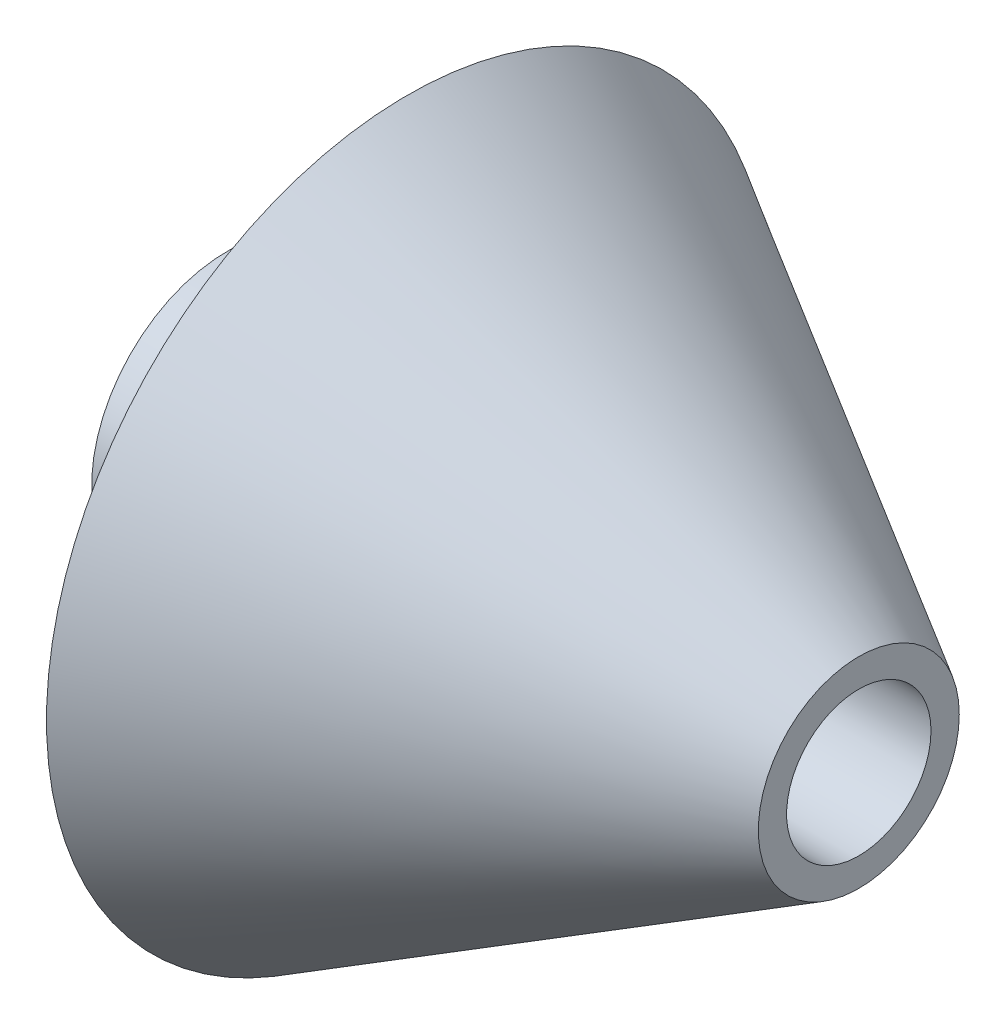
SolidWorks part; units mm, degrees
ref_plane "Alzado" through (0, 0, 0) normal (0, 0, 1) x (1, 0, 0)
ref_plane "Planta" through (0, 0, 0) normal (0, 1, 0) x (1, 0, 0)
ref_plane "Vista lateral" through (0, 0, 0) normal (1, 0, 0) x (0, 0, -1)
sketch "Croquis1" plane through (0, 0, 0) normal (1, 0, 0) x (0, 0, -1)
  line L0 (0, 7.5) -> (0, -7.5) construction
  line L1 (-7.5, 0) -> (7.5, 0) construction
  circle A0 centre (0, 0) radius 7.5
  dimension "D1" = 15
extrude "Saliente-Extruir1" add sketch "Croquis1" along normal blind 10
sketch "Croquis2" plane through (10, 0, 0) normal (1, 0, 0) x (0, 0, -1)
  circle A0 centre (0, 0) radius 20
  dimension "D1" = 40
extrude "Saliente-Extruir2" add sketch "Croquis2" along normal blind 25 draft 30
sketch "Croquis3" plane through (35, 0, 0) normal (1, 0, 0) x (0, 0, -1)
  circle A0 centre (0, 0) radius 4
  dimension "D1" = 8
extrude "Cortar-Extruir2" cut sketch "Croquis3" against normal blind 70
hole_wizard "Taladro de margen para #81" positions "Croquis3D1" profile "Croquis4" hole size "#8" standard "Ansi Inch" end condition up to next
sketch3d "Croquis3D1"
  point P0 (5, 7.4812, -0.5307)
  dimension "D1" = 5
sketch "Croquis4" plane through (5, 7.4812, -0.5307) normal (1, 0, 0) x (0, 0.0708, 0.9975)
  line L0 (0, 0) -> (0, 3.5)
  line L1 (0, 3.5) -> (2.2479, 3.5)
  line L2 (2.2479, 3.5) -> (2.2479, 0)
  line L5 (2.2479, 0) -> (0, 0)
  line L11 (0, -6.35) -> (0, 107.95) construction
  dimension "Diámetro de taladro hasta el siguiente" = 4.4958
  dimension "Profundidad de taladro hasta el siguiente" = 3.5
